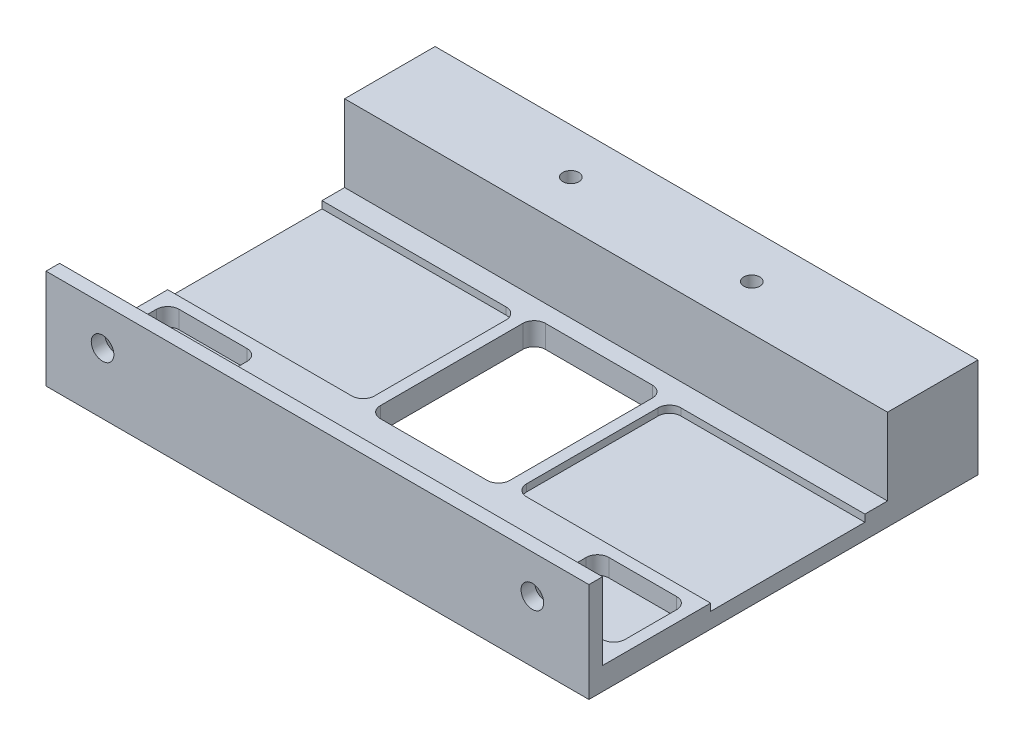
SolidWorks part; units mm, degrees
material "1345 Alloy"
ref_plane "Front Plane" through (0, 0, 0) normal (0, 0, 1) x (1, 0, 0)
ref_plane "Top Plane" through (0, 0, 0) normal (0, 1, 0) x (1, 0, 0)
ref_plane "Right Plane" through (0, 0, 0) normal (1, 0, 0) x (0, 0, -1)
sketch "Sketch1" plane through (0, 0, 0) normal (0, 1, 0) x (1, 0, 0)
  line L1 (-38.1, 21.9075) -> (38.1, 21.9075)
  line L2 (-38.1, 21.9075) -> (-38.1, -21.9075)
  line L3 (-38.1, -21.9075) -> (38.1, -21.9075)
  line L4 (38.1, 21.9075) -> (38.1, -21.9075)
  line L5 (-38.1, 21.9075) -> (38.1, -21.9075) construction
  line L6 (-38.1, -21.9075) -> (38.1, 21.9075) construction
  point P0 (0, 0)
  dimension "D1" = 43.815
  dimension "D2" = 76.2
extrude "Boss-Extrude1" add sketch "Sketch1" along normal blind 3.175
sketch "Sketch2" plane through (0, 3.175, 0) normal (0, 1, 0) x (1, 0, 0)
  line L0 (38.1, -21.9075) -> (38.1, 21.9075) construction
  line L1 (-38.1, 21.9075) -> (38.1, 21.9075)
  line L2 (-38.1, 21.9075) -> (-38.1, 20.0025)
  line L3 (-38.1, 20.0025) -> (38.1, 20.0025)
  line L4 (38.1, 21.9075) -> (38.1, 20.0025)
  line L5 (-38.1, 0) -> (38.1, 0) construction
  line L6 (-38.1, 21.9075) -> (-38.1, -21.9075) construction
  line L7 (38.1, -21.9075) -> (38.1, -20.0025)
  line L8 (-38.1, -20.0025) -> (38.1, -20.0025)
  line L9 (-38.1, -21.9075) -> (-38.1, -20.0025)
  line L10 (-38.1, -21.9075) -> (38.1, -21.9075)
  dimension "D1" = 1.905
extrude "Boss-Extrude2" add sketch "Sketch2" along normal blind 10.795
sketch "Sketch6" plane through (0, 3.175, 0) normal (0, 1, 0) x (1, 0, 0)
  line L0 (-38.1, 20.0025) -> (-38.1, -20.0025) construction
  line L1 (38.1, -20.0025) -> (38.1, 20.0025) construction
  line L2 (-38.1, 20.0025) -> (38.1, 20.0025) construction
  line L3 (-7.5, 16.0025) -> (7.5, 16.0025) construction
  line L4 (-7.5, 16.0025) -> (-7.5, -3.9975) construction
  line L5 (-7.5, -3.9975) -> (7.5, -3.9975) construction
  line L6 (7.5, 16.0025) -> (7.5, -3.9975) construction
  line L7 (-38.1, 6.0025) -> (38.1, 6.0025) construction
  line L8 (-7.5, 16.0025) -> (7.5, -3.9975) construction
  line L9 (-7.5, -3.9975) -> (7.5, 16.0025) construction
  line L10 (-38.1, -7.9975) -> (38.1, -7.9975) construction
  line L12 (-9.0875, 16.0025) -> (-9.0875, -3.9975)
  line L13 (-7.5, -5.585) -> (7.5, -5.585)
  line L14 (9.0875, 16.0025) -> (9.0875, -3.9975)
  line L15 (-7.5, 17.59) -> (7.5, 17.59)
  line L16 (38.1, 20.0025) -> (38.1, -7.9975) construction
  line L17 (-38.1, 20.0025) -> (-38.1, -7.9975) construction
  line L18 (-9.0875, -5.585) -> (9.0875, -5.585) construction
  line L19 (-9.0875, 17.59) -> (-9.0875, -5.585) construction
  line L20 (9.0875, 17.59) -> (9.0875, -5.585) construction
  line L21 (-9.0875, 17.59) -> (9.0875, 17.59) construction
  arc A0 (-7.5, -5.585) -> (-9.0875, -3.9975) centre (-7.5, -3.9975) cw
  arc A1 (7.5, -5.585) -> (9.0875, -3.9975) centre (7.5, -3.9975) ccw
  arc A2 (9.0875, 16.0025) -> (7.5, 17.59) centre (7.5, 16.0025) ccw
  arc A3 (-7.5, 17.59) -> (-9.0875, 16.0025) centre (-7.5, 16.0025) ccw
  point P0 (0, 6.0025)
  dimension "D5" = 1.5875
  dimension "D1" = 15
  dimension "D2" = 20
  dimension "D3" = 28
  dimension "D4" = 1.5875
extrude "Cut-Extrude3" cut sketch "Sketch6" against normal through all
sketch "Sketch7" plane through (0, 3.175, 0) normal (0, 1, 0) x (1, 0, 0)
  line L0 (-38.1, 6.0025) -> (-10.675, 6.0025) construction
  line L1 (-38.1, 20.0025) -> (-38.1, -20.0025) construction
  line L2 (-38.1, 16.8275) -> (-10.675, 16.8275)
  line L3 (-38.1, 16.8275) -> (-38.1, -4.8225)
  line L4 (-38.1, -4.8225) -> (-10.675, -4.8225)
  line L5 (-38.1, 6.0025) -> (38.1, 6.0025) construction
  line L6 (-38.1, 20.0025) -> (38.1, 20.0025) construction
  line L7 (0, 17.59) -> (0, -5.585) construction
  line L8 (-10.675, 16.8275) -> (-10.675, -4.8225)
  line L10 (7.5, 17.59) -> (-7.5, 17.59) construction
  line L11 (-7.5, -5.585) -> (7.5, -5.585) construction
  line L12 (-9.0875, 16.0025) -> (-9.0875, -3.9975) construction
  line L13 (10.675, 16.8275) -> (10.675, -4.8225)
  line L14 (38.1, 16.8275) -> (10.675, 16.8275)
  line L15 (38.1, 6.0025) -> (10.675, 6.0025) construction
  line L16 (38.1, -4.8225) -> (10.675, -4.8225)
  line L17 (38.1, 16.8275) -> (38.1, -4.8225)
  dimension "D1" = 3.175
  dimension "D2" = 1.5875
extrude "Cut-Extrude4" cut sketch "Sketch7" against normal blind 1
sketch "Sketch11" plane through (0, 3.175, 0) normal (0, 1, 0) x (1, 0, 0)
  line L0 (0, 0) -> (0, -20.0025) construction
  line L1 (-36.5125, -6.41) -> (-36.5125, -16.8275)
  line L3 (38.1, -20.0025) -> (-38.1, -20.0025) construction
  line L4 (-38.1, -4.8225) -> (-38.1, -20.0025) construction
  line L6 (-36.5125, -16.8275) -> (-23.8125, -16.8275)
  line L7 (-23.8125, -16.8275) -> (-23.8125, -6.41)
  line L8 (-23.8125, -6.41) -> (-36.5125, -6.41)
  line L9 (-38.1, -4.8225) -> (-10.675, -4.8225) construction
  line L10 (23.8125, -6.41) -> (36.5125, -6.41)
  line L11 (23.8125, -16.8275) -> (23.8125, -6.41)
  line L12 (36.5125, -16.8275) -> (23.8125, -16.8275)
  line L13 (36.5125, -6.41) -> (36.5125, -16.8275)
  dimension "D1" = 1.5875
  dimension "D2" = 1.5875
  dimension "D3" = 12.7
  dimension "D4" = 3.175
extrude "Cut-Extrude6" cut sketch "Sketch11" against normal blind 2.5
sketch "Sketch13" plane through (0, 0, -20.0025) normal (0, 0, 1) x (1, 0, 0)
  line L4 (-38.1, 0) -> (38.1, 0)
  line L5 (-38.1, 13.97) -> (-38.1, 0)
  line L6 (38.1, 13.97) -> (-38.1, 13.97)
  line L7 (38.1, 0) -> (38.1, 13.97)
  line L8 (-38.1, 0) -> (38.1, 0)
  line L9 (-38.1, 13.97) -> (-38.1, 0)
  line L10 (38.1, 13.97) -> (-38.1, 13.97)
  line L11 (38.1, 0) -> (38.1, 13.97)
  dimension "D1" = 0
extrude "Boss-Extrude3" add sketch "Sketch13" against normal blind 12.7
sketch "Sketch14" plane through (0, 0, 20.0025) normal (0, 0, -1) x (-1, 0, 0)
  line L0 (0, 3.175) -> (0, 13.97) construction
  line L5 (-38.1, 3.175) -> (38.1, 3.175) construction
  line L6 (-38.1, 13.97) -> (38.1, 13.97) construction
  line L9 (30.1625, 3.175) -> (30.1625, 13.97) construction
  circle A0 centre (30.1625, 8.5725) radius 1.5875
  circle A1 centre (-30.1625, 8.5725) radius 1.5875
  dimension "D1" = 3.175
extrude "Cut-Extrude7" cut sketch "Sketch14" against normal up to surface (1.905 mm away) up to face at (0, 6.985, 21.9075)
sketch3d "3DSketch1"
  line L0 (-30.1625, 3.175, 16.8275) -> (-30.1625, 3.175, 20.0025) construction
  line L1 (-36.5125, 3.175, 16.8275) -> (-23.8125, 3.175, 16.8275) construction
  line L2 (38.1, 3.175, 20.0025) -> (-38.1, 3.175, 20.0025) construction
  line L3 (-30.1625, 3.175, 20.0025) -> (-30.1625, 13.97, 20.0025) construction
  line L4 (38.1, 13.97, 20.0025) -> (-38.1, 13.97, 20.0025) construction
fillet "Fillet1" radius 1.5875 12 edges at (-36.5125, 1.925, 6.41) (-23.8125, 1.925, 6.41) (23.8125, 1.925, 16.8275) (36.5125, 1.925, 16.8275) (23.8125, 1.925, 6.41) (36.5125, 1.925, 6.41) (-36.5125, 1.925, 16.8275) (-23.8125, 1.925, 16.8275) (-10.675, 2.675, 4.8225) (-10.675, 2.675, -16.8275) (10.675, 2.675, -16.8275) (10.675, 2.675, 4.8225)
hole_wizard "1/4-20 Tapped Hole1" positions "Sketch16" profile "Sketch15" tap size "1/4-20" standard "Ansi Inch"
sketch "Sketch16" plane through (0, 0, -32.7025) normal (0, 0, -1) x (-1, 0, 0)
  line L0 (0, 0) -> (0, 13.97) construction
  line L1 (38.1, 0) -> (-38.1, 0) construction
  line L2 (-38.1, 13.97) -> (38.1, 13.97) construction
  line L4 (0, 6.985) -> (-38.1, 6.985) construction
  line L5 (-38.1, 0) -> (-38.1, 13.97) construction
  point P0 (-25.4521, 6.985)
  point P16 (25.4521, 6.985)
sketch "Sketch15" plane through (25.4521, 6.985, -32.7025) normal (1, 0, 0) x (0, 1, 0)
  line L0 (0, 0) -> (0, 7.8838)
  line L1 (0, 7.8838) -> (2.5527, 6.35)
  line L2 (2.5527, 6.35) -> (2.5527, 0)
  line L5 (2.5527, 0) -> (0, 0)
  line L10 (0, 7.8838) -> (-2.5527, 6.35) construction
  line L11 (0, -6.35) -> (0, 107.95) construction
  dimension "Tap Drill Dia." = 5.1054
  dimension "Tap Drill Depth" = 6.35
  dimension "Drill Angle" = 118
cosmetic thread "Hole Thread1" parameters "D1"=6.35, "D2"=6.35
cosmetic thread "Hole Thread2" parameters "D1"=6.35, "D2"=6.35
hole_wizard "#4-40 Tapped Hole1" positions "Sketch18" profile "Sketch17" tap size "#4-40" standard "Ansi Inch"
sketch "Sketch18" plane through (0, 13.97, 0) normal (0, 1, 0) x (-1, 0, 0)
  point P6 (12.7, -26.3525)
  point P10 (-12.7, -26.3525)
sketch "Sketch17" plane through (-12.7, 13.97, -26.3525) normal (1, 0, 0) x (0, 0, 1)
  line L0 (0, 0) -> (0, 7.0292)
  line L1 (0, 7.0292) -> (1.1303, 6.35)
  line L2 (1.1303, 6.35) -> (1.1303, 0)
  line L5 (1.1303, 0) -> (0, 0)
  line L10 (0, 7.0292) -> (-1.1303, 6.35) construction
  line L11 (0, -6.35) -> (0, 107.95) construction
  dimension "Tap Drill Dia." = 2.2606
  dimension "Tap Drill Depth" = 6.35
  dimension "Drill Angle" = 118
cosmetic thread "Hole Thread3" parameters "D1"=6.35, "D2"=2.8448
cosmetic thread "Hole Thread4" parameters "D1"=6.35, "D2"=2.8448
